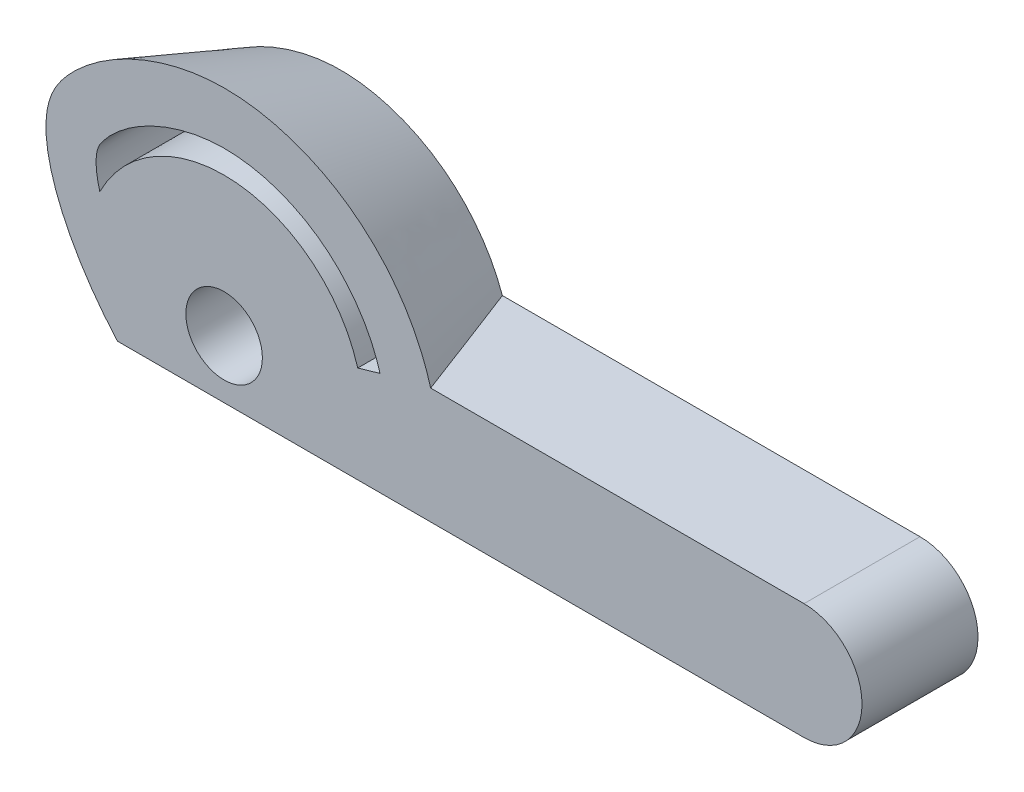
SolidWorks part; units mm, degrees
ref_plane "Plano frontal" through (0, 0, 0) normal (0, 0, 1) x (1, 0, 0)
ref_plane "Plano superior" through (0, 0, 0) normal (0, 1, 0) x (1, 0, 0)
ref_plane "Plano direito" through (0, 0, 0) normal (1, 0, 0) x (0, 0, -1)
sketch "Esboço2" plane through (0, 0, 0) normal (0, 0, 1) x (1, 0, 0)
  line L0 (25, 2.5) -> (8.9058, 2.5)
  line L1 (25, -2.5) -> (4.3301, -2.5)
  line L2 (0, 0) -> (-3.2897, -3.7653) construction
  line L3 (0, 0) -> (-6.9659, 6.086) construction
  line L4 (6.721, 1.9566) -> (5.7608, 1.6771)
  arc A0 (25, -2.5) -> (25, 2.5) centre (25, 0) ccw
  circle A1 centre (0, 0) radius 1.65
  circle A2 centre (0, 0) radius 5 construction
  circle A3 centre (0, 0) radius 9.25 construction
  arc A5 (5.7608, 1.6771) -> (-5.3572, 2.702) centre (0, 0) ccw
  spline S0 degree 3 poles (4.3301, -2.5) (3.6274, -3.6971) (1.501, -5.3032) (-1.714, -4.9157) (-5.419, -2.304) (-9.0198, 3.4922) (-5.6751, 7.7775) (-1.7732, 9.5205) (2.2606, 9.1278) (6.2171, 7.429) (8.2601, 4.7846) (8.9058, 2.5) knots 0 0 0 0 0.103912 0.19054 0.222509 0.458861 0.503374 0.667648 0.751689 0.822132 1 1 1 1
  spline S2 degree 3 poles (-5.3572, 2.702) (-5.4268, 2.952) (-5.537, 3.5036) (-5.5155, 4.0279) (-5.4336, 4.3121) (-5.3182, 4.5533) (-4.8932, 5.077) (-4.1605, 5.6883) (-3.3164, 6.2003) (-2.3784, 6.604) (-1.062, 6.9701) (0.5465, 7.0733) (2.4428, 6.6516) (4.1692, 5.7362) (5.3441, 4.5956) (6.0769, 3.5177) (6.4298, 2.8093) (6.6261, 2.272) (6.6962, 2.0444) (6.7184, 1.966) (6.721, 1.9566) knots 0.381365 0.381365 0.381365 0.381365 0.405878 0.439299 0.456009 0.472719 0.506139 0.53956 0.57298 0.6064 0.639821 0.706661 0.773502 0.840343 0.907183 0.940604 0.974024 0.990734 0.998956 1 1 1 1
  dimension "D1" = 3.3
  dimension "D2" = 10
  dimension "D3" = 18.5
  dimension "D4" = 2.5
  dimension "D7" = 12
  dimension "D5" = 25
extrude "Ressalto-extrusão1" add sketch "Esboço2" along normal blind 5
chamfer "Chanfro1" distance 5 angle 20 1 edges
sketch "Esboço3" plane through (0, 0, 5) normal (0, 0, 1) x (1, 0, 0)
  line L0 (1.9625, -2.5) -> (25, -2.5) construction
  line L1 (7.7033, -2.5) -> (-9.1181, -2.5)
  line L2 (7.7033, -2.5) -> (7.7033, -6.3348)
  line L3 (7.7033, -6.3348) -> (-9.1181, -6.3348)
  line L4 (-9.1181, -2.5) -> (-9.1181, -6.3348)
extrude "Corte-extrusão1" cut sketch "Esboço3" against normal blind 5
